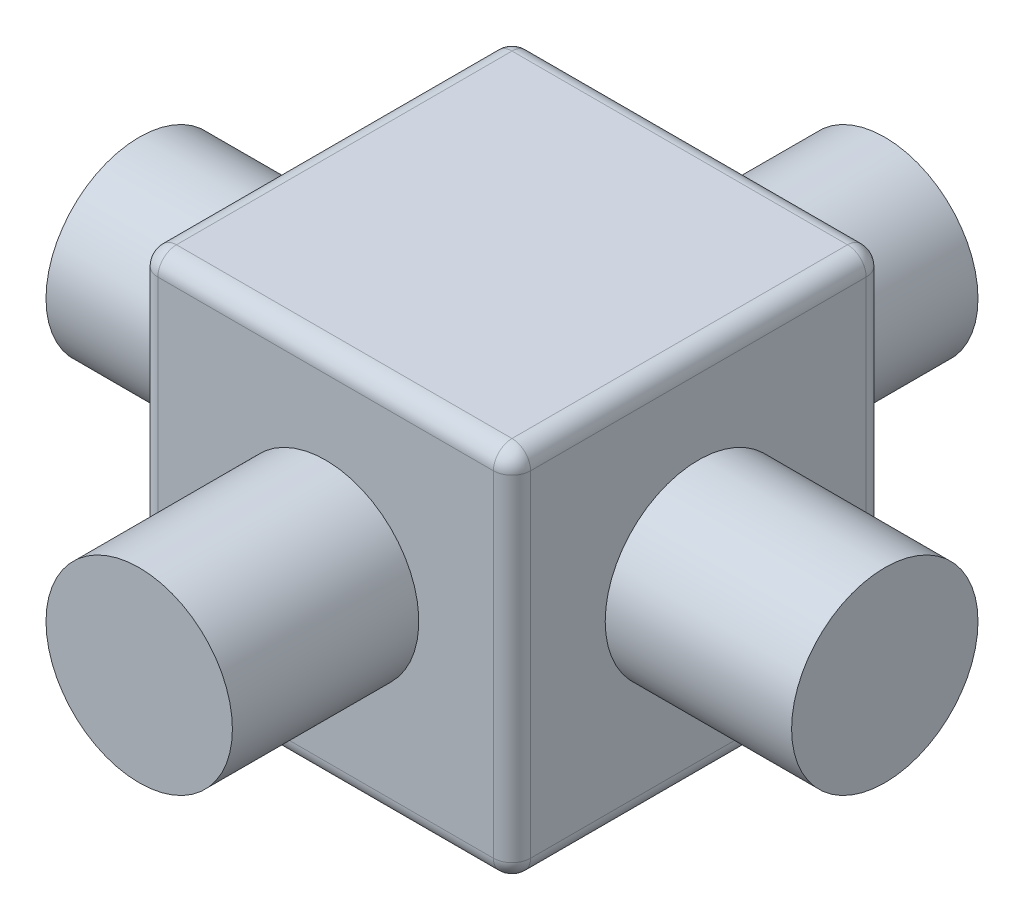
SolidWorks part; units mm, degrees
ref_plane "Front Plane" through (0, 0, 0) normal (0, 0, 1) x (1, 0, 0)
ref_plane "Top Plane" through (0, 0, 0) normal (0, 1, 0) x (1, 0, 0)
ref_plane "Right Plane" through (0, 0, 0) normal (1, 0, 0) x (0, 0, -1)
sketch "Sketch1" plane through (0, 0, 0) normal (0, 1, 0) x (1, 0, 0)
  line L1 (-3, -3) -> (3, -3)
  line L2 (-3, -3) -> (-3, 3)
  line L3 (-3, 3) -> (3, 3)
  line L4 (3, -3) -> (3, 3)
  line L5 (-3, -3) -> (3, 3) construction
  line L6 (-3, 3) -> (3, -3) construction
  point P0 (0, 0)
  dimension "D1" = 6
  dimension "D2" = 6
extrude "Boss-Extrude1" add sketch "Sketch1" along normal blind 6
fillet "Fillet1" radius 0.3 12 edges at (-3, 0, 0) (-3, 3, -3) (0, 0, -3) (3, 3, -3) (3, 0, 0) (-3, 3, 3) (3, 3, 3) (0, 0, 3) (0, 6, 3) (-3, 6, 0) (0, 6, -3) (3, 6, 0)
sketch "Sketch2" plane through (0, 0, -3) normal (0, 0, -1) x (-1, 0, 0)
  line L2 (-3, 0.3) -> (-3, 5.7) construction
  circle A0 centre (0, 3) radius 1.5
  point P5 (-0.7574, 3.0324)
  point P6 (-3, 3)
  point P10 (0.0631, 2.9187)
  dimension "D1" = 3
  dimension "D2" = 3
  dimension "D3" = 3
extrude "Boss-Extrude2" add sketch "Sketch2" along normal blind 3
ref_plane "Plane1" through (0, 0, 0) normal (0, 0, -1) x (-1, 0, 0)
ref_plane "Plane2" through (0, 0, 0) normal (1, 0, 0) x (0, 0, -1)
ref_axis "Axis1" through (0, 0.03, 0) along (0, 1, 0)
pattern_circular "CirPattern1" count 4 over 360 about axis through (0, 0.03, 0) along (0, 1, 0) of "Boss-Extrude2"
